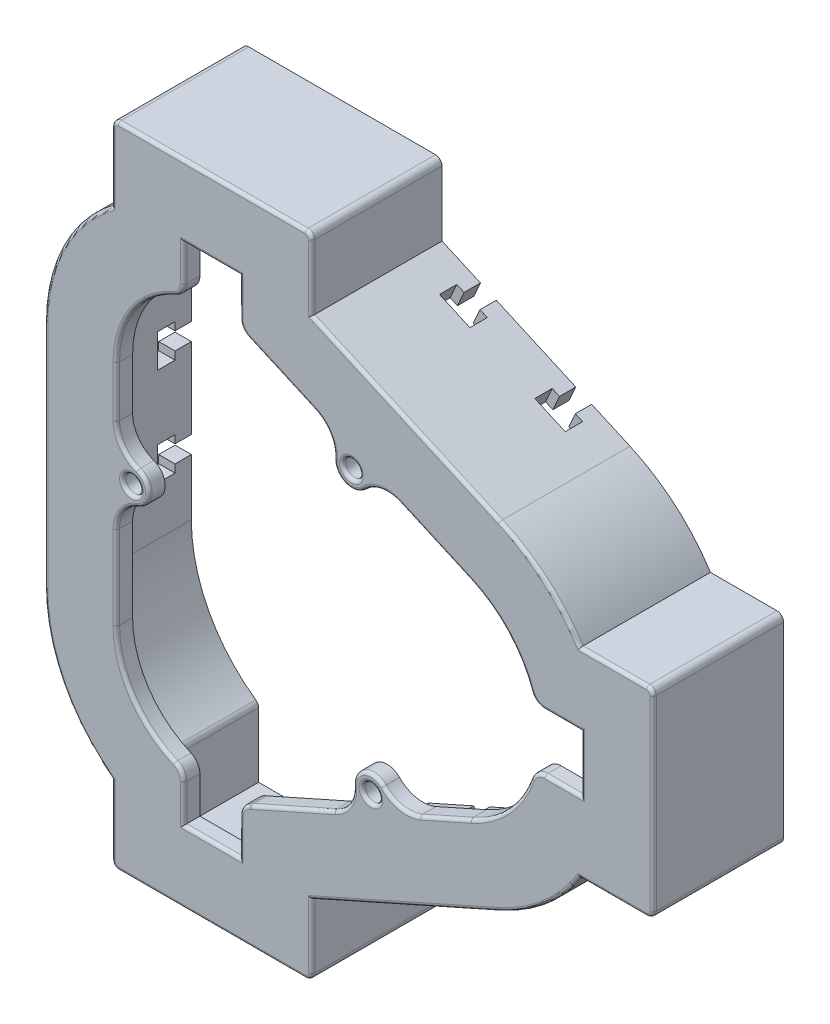
SolidWorks part; units mm, degrees
ref_plane "Front Plane" through (0, 0, 0) normal (0, 0, 1) x (1, 0, 0)
ref_plane "Top Plane" through (0, 0, 0) normal (0, 1, 0) x (1, 0, 0)
ref_plane "Right Plane" through (0, 0, 0) normal (1, 0, 0) x (0, 0, -1)
sketch "Sketch1" plane through (0, 0, -80.01) normal (0, 0, -1) x (-1, 0, 0)
  line L0 (14.1705, 137.7093) -> (22.108, 137.7093) construction
  line L1 (-128.3273, 40.8549) -> (-128.3273, 32.9174) construction
  line L2 (14.1705, -63.937) -> (22.108, -63.937) construction
  line L3 (55.2868, -7.5638) -> (55.2868, 81.3362)
  line L4 (29.093, 120.8247) -> (29.093, 135.1693)
  line L5 (29.093, 135.1693) -> (22.108, 135.1693)
  line L6 (14.1705, 135.1693) -> (22.108, 135.1693)
  line L7 (14.1705, 135.1693) -> (7.1855, 135.1693)
  line L8 (7.1855, 135.1693) -> (7.1855, 120.8247)
  line L9 (3.0278, 115.2711) -> (-82.5915, 77.144)
  line L10 (-111.5749, 47.8399) -> (-125.7873, 47.8399)
  line L11 (-125.7873, 47.8399) -> (-125.7873, 40.8549)
  line L12 (-125.7873, 40.8549) -> (-125.7873, 32.9174)
  line L13 (-125.7873, 32.9174) -> (-125.7873, 25.9324)
  line L14 (-125.7873, 25.9324) -> (-111.5749, 25.9324)
  line L15 (-82.5915, -3.3716) -> (3.0278, -41.4987)
  line L16 (7.1855, -47.0524) -> (7.1855, -61.397)
  line L17 (7.1855, -61.397) -> (14.1705, -61.397)
  line L18 (14.1705, -61.397) -> (22.108, -61.397)
  line L19 (22.108, -61.397) -> (29.093, -61.397)
  line L20 (29.093, -61.397) -> (29.093, -47.0524)
  line L21 (57.8268, -7.5638) -> (57.8268, 81.3362)
  line L22 (31.633, 120.8247) -> (31.633, 137.7093)
  line L23 (31.633, 137.7093) -> (22.108, 137.7093)
  line L24 (22.108, 137.7093) -> (22.108, 117.6323)
  line L25 (14.1705, 117.6323) -> (14.1705, 137.7093)
  line L26 (14.1705, 137.7093) -> (4.6455, 137.7093)
  line L27 (4.6455, 137.7093) -> (4.6455, 120.8247)
  line L28 (1.9945, 117.5914) -> (-83.6248, 79.4643)
  line L29 (-111.5749, 50.3799) -> (-128.3273, 50.3799)
  line L30 (-128.3273, 50.3799) -> (-128.3273, 40.8549)
  line L31 (-128.3273, 40.8549) -> (-106.0032, 40.8549)
  line L32 (-106.0032, 32.9174) -> (-128.3273, 32.9174)
  line L33 (-128.3273, 32.9174) -> (-128.3273, 23.3924)
  line L34 (-128.3273, 23.3924) -> (-111.5749, 23.3924)
  line L35 (-83.6248, -5.692) -> (1.9945, -43.8191)
  line L36 (4.6455, -47.0524) -> (4.6455, -63.937)
  line L37 (4.6455, -63.937) -> (14.1705, -63.937)
  line L38 (14.1705, -63.937) -> (14.1705, -43.86)
  line L39 (22.108, -43.86) -> (22.108, -63.937)
  line L40 (22.108, -63.937) -> (31.633, -63.937)
  line L41 (31.633, -63.937) -> (31.633, -47.0524)
  line L42 (57.8268, -7.5638) -> (57.8268, 81.3362) construction
  line L43 (31.633, 120.8247) -> (31.633, 137.7093) construction
  line L44 (31.633, 137.7093) -> (22.108, 137.7093) construction
  line L47 (14.1705, 137.7093) -> (4.6455, 137.7093) construction
  line L48 (4.6455, 137.7093) -> (4.6455, 120.8247) construction
  line L49 (1.9945, 117.5914) -> (-83.6248, 79.4643) construction
  line L50 (-111.5749, 50.3799) -> (-128.3273, 50.3799) construction
  line L51 (-128.3273, 50.3799) -> (-128.3273, 40.8549) construction
  line L54 (-128.3273, 32.9174) -> (-128.3273, 23.3924) construction
  line L55 (-128.3273, 23.3924) -> (-111.5749, 23.3924) construction
  line L56 (-83.6248, -5.692) -> (1.9945, -43.8191) construction
  line L57 (4.6455, -47.0524) -> (4.6455, -63.937) construction
  line L58 (4.6455, -63.937) -> (14.1705, -63.937) construction
  line L61 (22.108, -63.937) -> (31.633, -63.937) construction
  line L62 (31.633, -63.937) -> (31.633, -47.0524) construction
  line L63 (83.2268, -7.5638) -> (83.2268, 81.3362)
  line L64 (57.033, 133.5249) -> (57.033, 163.1093)
  line L65 (57.033, 163.1093) -> (22.108, 163.1093)
  line L66 (14.1705, 163.1093) -> (22.108, 163.1093)
  line L67 (14.1705, 163.1093) -> (-20.7545, 163.1093)
  line L68 (-20.7545, 163.1093) -> (-20.7545, 135.2657)
  line L69 (-20.7545, 135.2657) -> (-93.9575, 102.6677)
  line L70 (-125.2661, 75.7799) -> (-153.7273, 75.7799)
  line L71 (-153.7273, 75.7799) -> (-153.7273, 40.8549)
  line L72 (-153.7273, 40.8549) -> (-153.7273, 32.9174)
  line L73 (-153.7273, 32.9174) -> (-153.7273, -2.0076)
  line L74 (-153.7273, -2.0076) -> (-125.2661, -2.0076)
  line L75 (-93.9575, -28.8953) -> (-20.7545, -61.4933)
  line L76 (-20.7545, -61.4933) -> (-20.7545, -89.337)
  line L77 (-20.7545, -89.337) -> (14.1705, -89.337)
  line L78 (14.1705, -89.337) -> (22.108, -89.337)
  line L79 (22.108, -89.337) -> (57.033, -89.337)
  line L80 (57.033, -89.337) -> (57.033, -59.7525)
  line L81 (76.8768, -7.5638) -> (76.8768, 81.3362)
  line L82 (50.683, 130.234) -> (50.683, 156.7593)
  line L83 (50.683, 156.7593) -> (22.108, 156.7593)
  line L84 (14.1705, 156.7593) -> (22.108, 156.7593)
  line L85 (14.1705, 156.7593) -> (-14.4045, 156.7593)
  line L86 (-14.4045, 156.7593) -> (-14.4045, 131.1423)
  line L87 (-14.4045, 131.1423) -> (-91.3743, 96.8669)
  line L88 (-121.6907, 69.4299) -> (-147.3773, 69.4299)
  line L89 (-147.3773, 69.4299) -> (-147.3773, 40.8549)
  line L90 (-147.3773, 40.8549) -> (-147.3773, 32.9174)
  line L91 (-147.3773, 32.9174) -> (-147.3773, 4.3424)
  line L92 (-147.3773, 4.3424) -> (-121.6907, 4.3424)
  line L93 (-91.3743, -23.0945) -> (-14.4045, -57.3699)
  line L94 (-14.4045, -57.3699) -> (-14.4045, -82.987)
  line L95 (-14.4045, -82.987) -> (14.1705, -82.987)
  line L96 (14.1705, -82.987) -> (22.108, -82.987)
  line L97 (22.108, -82.987) -> (50.683, -82.987)
  line L98 (50.683, -82.987) -> (50.683, -56.4617)
  line L99 (49.3813, 43.2476) -> (49.3813, 81.3362) construction
  line L100 (49.3813, 81.3362) -> (57.8268, 81.3362) construction
  circle A3 centre (18.1393, 81.3362) radius 19.05 construction
  circle A4 centre (18.1393, -7.5638) radius 47.625 construction
  circle A5 centre (-58.3701, 37.7264) radius 19.05 construction
  arc A6 (-29.3254, 43.8149) -> (-88.2162, 25.2292) centre (-58.7708, 34.522) ccw construction
  arc A7 (-29.3254, 43.8149) -> (-88.2162, 25.2292) centre (-58.7708, 34.522) ccw construction
  arc A8 (-89.1699, 24.9282) -> (-28.3718, 44.1159) centre (-58.7708, 34.522) ccw construction
  arc A9 (-89.1699, 24.9282) -> (-28.3718, 44.1159) centre (-58.7708, 34.522) ccw construction
  circle A10 centre (18.1393, 76.2562) radius 36.5125 construction
  circle A11 centre (18.1393, 76.2562) radius 36.5125 construction
  circle A12 centre (49.3813, 43.2476) radius 3.3782
  circle A13 centre (-43.805, -14.1791) radius 3.3782
  circle A14 centre (-36.2365, 91.4312) radius 3.3782
  arc A15 (33.5733, -44.1273) -> (57.8268, -7.5638) centre (18.1393, -7.5638) ccw
  arc A16 (57.8268, 81.3362) -> (33.5733, 117.8997) centre (18.1393, 81.3362) ccw
  arc A17 (31.633, 120.8247) -> (33.5733, 117.8997) centre (34.808, 120.8247) ccw
  arc A18 (14.1705, 117.6323) -> (22.108, 117.6323) centre (18.1393, 81.3362) ccw
  arc A19 (2.7053, 117.8997) -> (4.6455, 120.8247) centre (1.4705, 120.8247) ccw
  arc A20 (2.7053, 117.8997) -> (1.9945, 117.5914) centre (18.1393, 81.3362) ccw
  arc A21 (-83.6248, 79.4643) -> (-108.5831, 52.4919) centre (-64.6643, 36.8862) ccw
  arc A22 (-111.5749, 50.3799) -> (-108.5831, 52.4919) centre (-111.5749, 53.5549) ccw
  arc A23 (-106.0032, 32.9174) -> (-106.0032, 40.8549) centre (-64.6643, 36.8862) ccw
  arc A24 (-108.5831, 21.2805) -> (-111.5749, 23.3924) centre (-111.5749, 20.2174) ccw
  arc A25 (-108.5831, 21.2805) -> (-83.6248, -5.692) centre (-64.6643, 36.8862) ccw
  arc A26 (1.9945, -43.8191) -> (2.7053, -44.1273) centre (18.1393, -7.5638) ccw
  arc A27 (4.6455, -47.0524) -> (2.7053, -44.1273) centre (1.4705, -47.0524) ccw
  arc A28 (22.108, -43.86) -> (14.1705, -43.86) centre (18.1393, -7.5638) ccw
  arc A29 (33.5733, -44.1273) -> (31.633, -47.0524) centre (34.808, -47.0524) ccw
  arc A30 (33.5733, -44.1273) -> (57.8268, -7.5638) centre (18.1393, -7.5638) ccw construction
  arc A31 (57.8268, 81.3362) -> (33.5733, 117.8997) centre (18.1393, 81.3362) ccw construction
  arc A32 (31.633, 120.8247) -> (33.5733, 117.8997) centre (34.808, 120.8247) ccw construction
  arc A34 (2.7053, 117.8997) -> (4.6455, 120.8247) centre (1.4705, 120.8247) ccw construction
  arc A35 (2.7053, 117.8997) -> (1.9945, 117.5914) centre (18.1393, 81.3362) ccw construction
  arc A36 (-83.6248, 79.4643) -> (-108.5831, 52.4919) centre (-64.6643, 36.8862) ccw construction
  arc A37 (-111.5749, 50.3799) -> (-108.5831, 52.4919) centre (-111.5749, 53.5549) ccw construction
  arc A39 (-108.5831, 21.2805) -> (-111.5749, 23.3924) centre (-111.5749, 20.2174) ccw construction
  arc A40 (-108.5831, 21.2805) -> (-83.6248, -5.692) centre (-64.6643, 36.8862) ccw construction
  arc A41 (1.9945, -43.8191) -> (2.7053, -44.1273) centre (18.1393, -7.5638) ccw construction
  arc A42 (4.6455, -47.0524) -> (2.7053, -44.1273) centre (1.4705, -47.0524) ccw construction
  arc A44 (33.5733, -44.1273) -> (31.633, -47.0524) centre (34.808, -47.0524) ccw construction
  arc A45 (-25.2473, 23.811) -> (-27.1386, 19.0962) centre (-64.6643, 36.8862) ccw construction
  arc A46 (-25.2473, 23.811) -> (-27.1386, 19.0962) centre (-64.6643, 36.8862) ccw construction
  circle A47 centre (-43.805, -14.1791) radius 6.7564
  circle A48 centre (49.3813, 43.2476) radius 6.7564
  circle A49 centre (-36.2365, 91.4312) radius 6.7564
  arc A50 (32.5855, -41.7872) -> (55.2868, -7.5638) centre (18.1393, -7.5638) ccw
  arc A51 (55.2868, 81.3362) -> (32.5855, 115.5596) centre (18.1393, 81.3362) ccw
  arc A52 (29.093, 120.8247) -> (32.5855, 115.5596) centre (34.808, 120.8247) ccw
  arc A53 (3.693, 115.5596) -> (7.1855, 120.8247) centre (1.4705, 120.8247) ccw
  arc A54 (3.693, 115.5596) -> (3.0278, 115.2711) centre (18.1393, 81.3362) ccw
  arc A55 (-82.5915, 77.144) -> (-106.1897, 51.6414) centre (-64.6643, 36.8862) ccw
  arc A56 (-111.5749, 47.8399) -> (-106.1897, 51.6414) centre (-111.5749, 53.5549) ccw
  arc A57 (-106.1897, 22.1309) -> (-111.5749, 25.9324) centre (-111.5749, 20.2174) ccw
  arc A58 (-106.1897, 22.1309) -> (-82.5915, -3.3716) centre (-64.6643, 36.8862) ccw
  arc A59 (3.0278, -41.4987) -> (3.693, -41.7872) centre (18.1393, -7.5638) ccw
  arc A60 (7.1855, -47.0524) -> (3.693, -41.7872) centre (1.4705, -47.0524) ccw
  arc A61 (32.5855, -41.7872) -> (29.093, -47.0524) centre (34.808, -47.0524) ccw
  arc A62 (57.033, -59.7525) -> (83.2268, -7.5638) centre (18.1393, -7.5638) ccw
  arc A63 (83.2268, 81.3362) -> (57.033, 133.5249) centre (18.1393, 81.3362) ccw
  arc A64 (57.033, 133.5249) -> (57.033, 133.5249) centre (57.033, 133.5249) ccw
  arc A65 (-20.7545, 135.2657) -> (-20.7545, 135.2657) centre (-20.7545, 135.2657) ccw
  arc A66 (-20.7545, 135.2657) -> (-20.7545, 135.2657) centre (-20.7545, 135.2657) cw
  arc A67 (-93.9575, 102.6677) -> (-125.2661, 75.7799) centre (-64.6643, 36.8862) ccw
  arc A68 (-125.2661, 75.7799) -> (-125.2661, 75.7799) centre (-125.2661, 75.7799) ccw
  arc A69 (-125.2661, -2.0076) -> (-125.2661, -2.0076) centre (-125.2661, -2.0076) ccw
  arc A70 (-125.2661, -2.0076) -> (-93.9575, -28.8953) centre (-64.6643, 36.8862) ccw
  arc A71 (-20.7545, -61.4933) -> (-20.7545, -61.4933) centre (-20.7545, -61.4933) cw
  arc A72 (-20.7545, -61.4933) -> (-20.7545, -61.4933) centre (-20.7545, -61.4933) ccw
  arc A73 (57.033, -59.7525) -> (57.033, -59.7525) centre (57.033, -59.7525) ccw
  arc A74 (50.683, -56.4617) -> (76.8768, -7.5638) centre (18.1393, -7.5638) ccw
  arc A75 (76.8768, 81.3362) -> (50.683, 130.234) centre (18.1393, 81.3362) ccw
  arc A76 (50.683, 130.234) -> (50.683, 130.234) centre (50.683, 130.234) ccw
  arc A77 (-14.4045, 131.1423) -> (-14.4045, 131.1423) centre (-14.4045, 131.1423) ccw
  arc A78 (-14.4045, 131.1423) -> (-14.4045, 131.1423) centre (-14.4045, 131.1423) cw
  arc A79 (-91.3743, 96.8669) -> (-121.6907, 69.4299) centre (-64.6643, 36.8862) ccw
  arc A80 (-121.6907, 69.4299) -> (-121.6907, 69.4299) centre (-121.6907, 69.4299) ccw
  arc A81 (-121.6907, 4.3424) -> (-121.6907, 4.3424) centre (-121.6907, 4.3424) ccw
  arc A82 (-121.6907, 4.3424) -> (-91.3743, -23.0945) centre (-64.6643, 36.8862) ccw
  arc A83 (-14.4045, -57.3699) -> (-14.4045, -57.3699) centre (-14.4045, -57.3699) cw
  arc A84 (-14.4045, -57.3699) -> (-14.4045, -57.3699) centre (-14.4045, -57.3699) ccw
  arc A85 (50.683, -56.4617) -> (50.683, -56.4617) centre (50.683, -56.4617) ccw
  point P5 (48.3895, 44.1159)
  point P68 (-40.8151, 98.5279)
  arc M83 (33.5733, -44.1273) -> (57.8268, -7.5638) centre (18.1393, -7.5638) ccw
  line M84 (57.8268, -7.5638) -> (57.8268, 81.3362)
  arc M85 (57.8268, 81.3362) -> (33.5733, 117.8997) centre (18.1393, 81.3362) ccw
  arc M86 (33.5733, 117.8997) -> (31.633, 120.8247) centre (34.808, 120.8247) cw
  line M87 (31.633, 120.8247) -> (31.633, 137.7093)
  line M88 (31.633, 137.7093) -> (22.108, 137.7093)
  line M89 (22.108, 137.7093) -> (22.108, 117.6323)
  line M91 (14.1705, 117.6323) -> (14.1705, 137.7093)
  line M92 (14.1705, 137.7093) -> (4.6455, 137.7093)
  line M93 (4.6455, 137.7093) -> (4.6455, 120.8247)
  arc M94 (4.6455, 120.8247) -> (2.7053, 117.8997) centre (1.4705, 120.8247) cw
  arc M95 (2.7053, 117.8997) -> (1.9945, 117.5914) centre (18.1393, 81.3362) ccw
  line M96 (1.9945, 117.5914) -> (-83.6248, 79.4643)
  arc M97 (-83.6248, 79.4643) -> (-108.5831, 52.4919) centre (-64.6643, 36.8862) ccw
  arc M98 (-108.5831, 52.4919) -> (-111.5749, 50.3799) centre (-111.5749, 53.5549) cw
  line M99 (-111.5749, 50.3799) -> (-128.3273, 50.3799)
  line M100 (-128.3273, 50.3799) -> (-128.3273, 40.8549)
  line M101 (-128.3273, 40.8549) -> (-106.0032, 40.8549)
  line M103 (-106.0032, 32.9174) -> (-128.3273, 32.9174)
  line M104 (-128.3273, 32.9174) -> (-128.3273, 23.3924)
  line M105 (-128.3273, 23.3924) -> (-111.5749, 23.3924)
  arc M106 (-111.5749, 23.3924) -> (-108.5831, 21.2805) centre (-111.5749, 20.2174) cw
  arc M107 (-108.5831, 21.2805) -> (-83.6248, -5.692) centre (-64.6643, 36.8862) ccw
  line M108 (-83.6248, -5.692) -> (1.9945, -43.8191)
  arc M109 (1.9945, -43.8191) -> (2.7053, -44.1273) centre (18.1393, -7.5638) ccw
  arc M110 (2.7053, -44.1273) -> (4.6455, -47.0524) centre (1.4705, -47.0524) cw
  line M111 (4.6455, -47.0524) -> (4.6455, -63.937)
  line M112 (4.6455, -63.937) -> (14.1705, -63.937)
  line M113 (14.1705, -63.937) -> (14.1705, -43.86)
  line M115 (22.108, -43.86) -> (22.108, -63.937)
  line M116 (22.108, -63.937) -> (31.633, -63.937)
  line M117 (31.633, -63.937) -> (31.633, -47.0524)
  arc M118 (31.633, -47.0524) -> (33.5733, -44.1273) centre (34.808, -47.0524) cw
  dimension "D2" = 6.7564
  dimension "D3" = 8.4455
  dimension "D4" = 8.4455
  dimension "D6" = 3.3782
  dimension "D5" = 38.0886
  dimension "D10" = 8.4455
  dimension "D1" = 0
  dimension "D7" = 2.54
  dimension "D8" = 25.4
  dimension "D9" = 19.05
extrude "Boss-Extrude1" add sketch "Sketch1" along normal blind 6.35 contours L3 A48 A12 | L9 A49 A14 | L15 A47 A13 | L92 A82 L93 L94 L95 L96 L97 L98 A74 L81 A75 L82 L83 L84 L85 L86 L87 A79 L88 L89 L90 L91 L18 L12 L6 M113 M112 M111 M110 M109 M108 M107 M106 M105 M104 M103 M101 M100 M99 M98 M97 M96 M95 M94 M93 M92 M91 M89 M88 M87 | L16 A60 A59 L15 A47 A58 A57 L14 L13 L17 M103 M104 M105 M106 M107 M108 M109 M110 M111 M112 M113 | A50 A61 L20 L19 L5 L4 A52 A51 L3 A48 M115 M116 M117 M118 M83 M84 M85 M86 M87 M88 M89 | L10 A56 A55 L9 A49 A54 A53 L8 L7 L11 M91 M92 M93 M94 M95 M96 M97 M98 M99 M100 M101 | L74 A70 L75 L76 L77 L78 L79 L80 A62 L63 A63 L64 L65 L66 L67 L68 L69 A67 L70 L71 L72 L73 A82 L92 L91 L90 L89 L88 A79 L87 L86 L85 L84 L83 L82 A75 L81 A74 L98 L97 L96 L95 L94 L93 | L3 A48 | L9 A49 | L15 A47 region at (-57.3347, 16.2007, -80.01) region at (-42.8101, 43.2476, -80.01) region at (-55.6291, 43.2476, -80.01) region at (-12.4476, -62.667, -80.01) region at (-10.678, 136.8923, -80.01) region at (46.3466, -19.8865, -80.01) region at (46.1297, -19.3994, -80.01) region at (31.3282, 95.7919, -80.01) region at (38.7539, 97.0843, -80.01) region at (-73.2165, -35.2073, -80.01) region at (-67.0221, -33.7495, -80.01)
extrude "Boss-Extrude2" add sketch "Sketch1<3>" along normal blind 50.8 contours L74 A70 L75 L76 L77 L78 L79 L80 A62 L63 A63 L64 L65 L66 L67 L68 L69 A67 L70 L71 L72 L73 A82 L92 L91 L90 L89 L88 A79 L87 L86 L85 L84 L83 L82 A75 L81 A74 L98 L97 L96 L95 L94 L93 region at (-73.2165, -35.2073, -80.01)
sketch "Sketch1<3>" plane through (0, 0, -80.01) normal (0, 0, -1) x (-1, 0, 0) same geometry as "Sketch1"
sketch "Sketch2" plane through (-83.2268, 0, 0) normal (-1, 0, 0) x (0, 0, 1)
  line L0 (-80.01, 36.8862) -> (-130.81, 36.8862) construction
  line L1 (-130.81, 395.458) -> (-130.81, 402.2144)
  line L2 (-80.01, -7.5638) -> (-80.01, 81.3362) construction
  line L3 (-130.81, -7.5638) -> (-130.81, 81.3362) construction
  line L4 (-130.81, 52.558) -> (-124.46, 52.558)
  line L5 (-124.46, 52.558) -> (-124.46, 49.4592)
  line L6 (-124.46, 49.4592) -> (-117.602, 49.4592)
  line L7 (-117.602, 49.4592) -> (-117.602, 62.4132)
  line L8 (-117.602, 55.9362) -> (-130.81, 55.9362) construction
  line L9 (-124.46, 62.4132) -> (-117.602, 62.4132)
  line L10 (-130.81, 59.3144) -> (-124.46, 59.3144)
  line L11 (-124.46, 59.3144) -> (-124.46, 62.4132)
  line L12 (-130.81, 14.458) -> (-124.46, 14.458)
  line L13 (-124.46, 14.458) -> (-124.46, 11.3592)
  line L14 (-124.46, 11.3592) -> (-117.602, 11.3592)
  line L15 (-117.602, 24.3132) -> (-117.602, 11.3592)
  line L16 (-124.46, 24.3132) -> (-117.602, 24.3132)
  line L17 (-124.46, 21.2144) -> (-124.46, 24.3132)
  line L18 (-130.81, 21.2144) -> (-124.46, 21.2144)
  line L19 (-130.81, 14.458) -> (-130.81, 21.2144)
  line L20 (-130.81, 52.558) -> (-130.81, 59.3144)
  line L21 (-130.81, 402.2144) -> (-124.46, 402.2144)
  line L22 (-124.46, 402.2144) -> (-124.46, 405.3132)
  line L23 (-124.46, 405.3132) -> (-117.602, 405.3132)
  line L24 (-117.602, 405.3132) -> (-117.602, 392.3592)
  line L25 (-124.46, 392.3592) -> (-117.602, 392.3592)
  line L26 (-124.46, 395.458) -> (-124.46, 392.3592)
  line L27 (-130.81, 395.458) -> (-124.46, 395.458)
  line L28 (-130.81, 433.558) -> (-130.81, 440.3144)
  line L29 (-130.81, 440.3144) -> (-124.46, 440.3144)
  line L30 (-124.46, 440.3144) -> (-124.46, 443.4132)
  line L31 (-124.46, 443.4132) -> (-117.602, 443.4132)
  line L32 (-117.602, 430.4592) -> (-117.602, 443.4132)
  line L33 (-124.46, 430.4592) -> (-117.602, 430.4592)
  line L34 (-124.46, 433.558) -> (-124.46, 430.4592)
  line L35 (-130.81, 433.558) -> (-124.46, 433.558)
  dimension "D1" = 6.858
  dimension "D2" = 6.7564
  dimension "D3" = 6.35
  dimension "D4" = 19.05
  dimension "D6" = 6.477
  dimension "D5" = 2
sketch "Sketch3" plane through (53.7017, 120.594, 0) normal (0.4068, 0.9135, 0) x (0.9135, -0.4068, 0)
  line L0 (4.0002, 130.81) -> (4.0002, 80.01) construction
  line L1 (-36.0663, 130.81) -> (44.0668, 130.81) construction
  line L2 (-36.0663, 80.01) -> (44.0668, 80.01) construction
  line L3 (24.3202, 130.81) -> (24.3202, 117.7036) construction
  line L4 (20.942, 130.81) -> (20.942, 124.46)
  line L5 (20.942, 124.46) -> (17.8432, 124.46)
  line L6 (17.8432, 124.46) -> (17.8432, 117.7036)
  line L7 (17.8432, 117.7036) -> (30.7972, 117.7036)
  line L8 (30.7972, 124.46) -> (30.7972, 117.7036)
  line L9 (27.6984, 124.46) -> (30.7972, 124.46)
  line L10 (27.6984, 130.81) -> (27.6984, 124.46)
  line L11 (-16.3198, 130.81) -> (-16.3198, 117.7036) construction
  line L12 (-19.698, 130.81) -> (-19.698, 124.46)
  line L13 (-12.9416, 130.81) -> (-12.9416, 124.46)
  line L14 (-19.698, 124.46) -> (-22.7968, 124.46)
  line L15 (-22.7968, 124.46) -> (-22.7968, 117.7036)
  line L16 (-12.9416, 124.46) -> (-9.8428, 124.46)
  line L17 (-9.8428, 124.46) -> (-9.8428, 117.7036)
  line L18 (-9.8428, 117.7036) -> (-22.7968, 117.7036)
  line L19 (-19.698, 130.81) -> (-12.9416, 130.81)
  line L20 (20.942, 130.81) -> (27.6984, 130.81)
  dimension "D1" = 3.3782
  dimension "D2" = 6.7564
  dimension "D3" = 6.35
  dimension "D4" = 6.477
  dimension "D5" = 20.32
extrude "Cut-Extrude1" cut sketch "Sketch3" against normal blind 18.542
ref_plane "Plane4" through (0, 36.8862, 0) normal (0, 1, 0) x (1, 0, 0)
mirror "Mirror1" about plane through (0, 36.8862, 0) normal (0, 1, 0) of "Cut-Extrude1"
extrude "Cut-Extrude2" cut sketch "Sketch2" against normal blind 18.542
fillet "Fillet1" radius 12.7 6 edges at (49.2059, -18.2386, -83.185) (43.2089, -20.9091, -83.185) (-55.2868, 46.53, -83.185) (-55.2868, 39.9652, -83.185) (41.7555, 95.3287, -83.185) (35.4409, 98.1406, -83.185)
fillet "Fillet2" radius 2.54 16 edges at (147.3773, 69.4299, -108.585) (147.3773, 4.3424, -108.585) (14.4045, 156.7593, -108.585) (-50.683, 156.7593, -108.585) (14.4045, 131.1423, -108.585) (-50.683, 130.234, -108.585) (14.4045, -57.3699, -108.585) (-50.683, -56.4617, -108.585) (20.7545, -89.337, -105.41) (-57.033, -89.337, -105.41) (-57.033, 163.1093, -105.41) (20.7545, 163.1093, -105.41) (153.7273, 75.7799, -105.41) (153.7273, -2.0076, -105.41) (121.6907, 4.3424, -108.585) (121.6907, 69.4299, -108.585)
fillet "Fillet3" radius 1.27 61 edges at (-56.2891, -88.593, -80.01) (-57.033, -73.2747, -80.01) (-76.3109, -36.7604, -80.01) (-83.2268, 36.8862, -80.01) (-76.3109, 110.5328, -80.01) (-57.033, 147.0471, -80.01) (-56.2891, 162.3654, -80.01) (-18.1393, 163.1093, -80.01) (20.0105, 162.3654, -80.01) (20.7545, 147.9175, -80.01) (57.356, 118.9667, -80.01) (111.5792, 91.5148, -80.01) (138.2267, 75.7799, -80.01) (152.9833, 75.036, -80.01) (153.7273, 36.8862, -80.01) (152.9833, -1.2636, -80.01) (138.2267, -2.0076, -80.01) (111.5792, -17.7424, -80.01) (57.356, -45.1943, -80.01) (20.7545, -74.1451, -80.01) (20.0105, -88.593, -80.01) (-18.1393, -89.337, -80.01) (32.8583, 91.4312, -80.01) (-52.7595, 43.2476, -80.01) (40.4268, -14.1791, -80.01) (118.6811, 47.8399, -80.01) (108.279, 48.886, -80.01) (97.0101, 66.8166, -80.01) (68.9051, 83.2387, -80.01) (47.712, 90.2142, -80.01) (33.488, 85.2591, -80.01) (27.6546, 99.1459, -80.01) (9.475, 109.7035, -80.01) (-3.3597, 115.417, -80.01) (-6.233, 117.6657, -80.01) (-7.1855, 127.997, -80.01) (-18.1393, 135.1693, -80.01) (-29.093, 127.997, -80.01) (-30.0455, 117.6657, -80.01) (-49.0955, 101.8702, -80.01) (-55.2868, 71.4076, -80.01) (-53.0179, 54.2346, -80.01) (-42.6249, 43.2476, -80.01) (-53.0179, 32.2606, -80.01) (-55.2868, 8.7262, -80.01) (-49.0955, -28.0979, -80.01) (-30.0455, -43.8933, -80.01) (-29.093, -54.2247, -80.01) (-18.1393, -61.397, -80.01) (-7.1855, -54.2247, -80.01) (-6.233, -43.8933, -80.01) (-3.3597, -41.6446, -80.01) (13.2624, -34.2446, -80.01) (35.2476, -21.9706, -80.01) (41.0565, -8.007, -80.01) (55.3212, -13.0317, -80.01) (72.7268, -7.7645, -80.01) (97.0101, 6.9558, -80.01) (108.279, 24.8863, -80.01) (118.6811, 25.9324, -80.01) (125.7873, 36.8862, -80.01)
equation "\"D4@Sketch1\"=\"D3@Sketch1\""
equation "\"D10@Sketch1\"=\"D3@Sketch1\""
